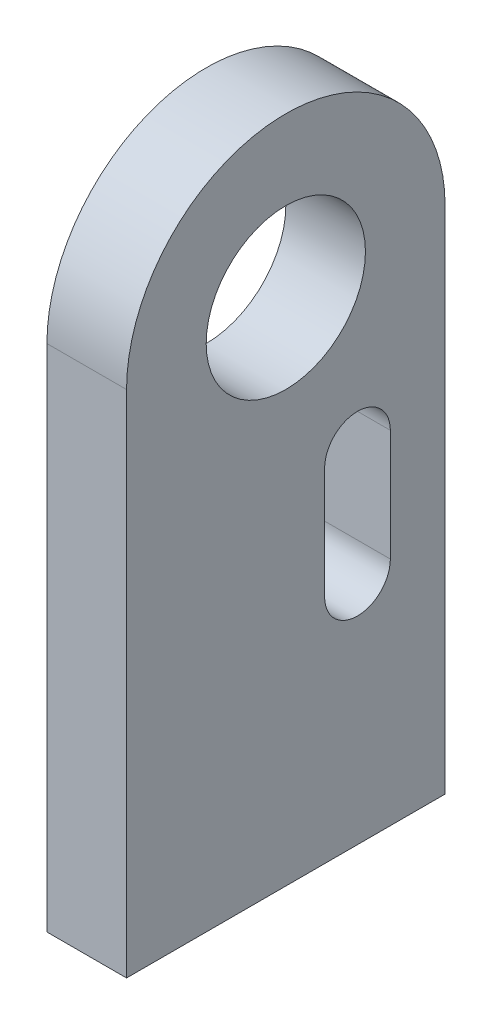
SolidWorks part; units mm, degrees
ref_plane "Front Plane" through (0, 0, 0) normal (0, 0, 1) x (1, 0, 0)
ref_plane "Top Plane" through (0, 0, 0) normal (0, 1, 0) x (1, 0, 0)
ref_plane "Right Plane" through (0, 0, 0) normal (1, 0, 0) x (0, 0, -1)
sketch "Sketch1" plane through (0, 0, 0) normal (1, 0, 0) x (0, 0, -1)
  line L0 (10, 0) -> (-10, 0)
  line L1 (-10, 32) -> (-10, 0)
  line L2 (0, 42) -> (0, 0) construction
  line L3 (10, 32) -> (10, 0)
  arc A0 (-10, 32) -> (10, 32) centre (0, 32) cw
  dimension "D1" = 10
extrude "Boss-Extrude1" add sketch "Sketch1" along normal blind 5 contours A0 L3 L0 L1
sketch "Sketch3" plane through (0, 0, 0) normal (-1, 0, 0) x (0, 0, 1)
  line L0 (-10, 32) -> (10, 32) construction
  line L1 (0, 32) -> (0, 0) construction
hole_wizard "Ø10.0mm Dowel Hole1" positions "3DSketch2" profile "Sketch4" hole size "Ø10.0" standard "ISO"
sketch3d "3DSketch2"
  point P0 (0, 32, 0)
sketch "Sketch4" plane through (0, 32, 0) normal (0, 1, 0) x (0, 0, 1)
  line L0 (0, 0) -> (0, 28.0043)
  line L1 (0, 28.0043) -> (5, 25)
  line L2 (5, 25) -> (5, 0)
  line L5 (5, 0) -> (0, 0)
  line L10 (0, 28.0043) -> (-5, 25) construction
  line L11 (0, -6.35) -> (0, 107.95) construction
  dimension "Hole Dia." = 10
  dimension "Hole Depth" = 25
  dimension "Drill Angle" = 118
sketch "Sketch5" plane through (5, 0, 0) normal (1, 0, 0) x (0, 0, -1)
  line L0 (0, 32) -> (10, 32) construction
  line L1 (10, 32) -> (-10, 32) construction
  line L2 (10, 0) -> (-10, 0) construction
  line L5 (4.5, 21.5) -> (4.5, 14.5) construction
  line L6 (6.5636, 21.5) -> (6.5636, 14.5)
  line L7 (2.4364, 21.5) -> (2.4364, 14.5)
  arc A0 (6.5636, 21.5) -> (2.4364, 21.5) centre (4.5, 21.5) ccw
  arc A1 (2.4364, 14.5) -> (6.5636, 14.5) centre (4.5, 14.5) ccw
  point P9 (4.5, 18)
  dimension "D1" = 18
extrude "Cut-Extrude1" cut sketch "Sketch5" against normal blind 10
sketch "Sketch6" plane through (0, 0, 0) normal (0, -1, 0) x (-1, 0, 0)
  line L0 (-2.5, -10) -> (-2.5, 10) construction
  line L1 (-5, -10) -> (0, -10) construction
  line L2 (-5, 10) -> (0, 10) construction
sketch "Sketch7" plane through (0, 0, 0) normal (0, -1, 0) x (-1, 0, 0)
  line L0 (0, 0) -> (-5, 0) construction
  line L1 (-5, 10) -> (-5, -10) construction
  line L2 (-2.5, 0) -> (-2.5, 5) construction
  line L3 (-2.5, 0) -> (-2.5, -5) construction
  dimension "D1" = 5
  dimension "D2" = 5
hole_wizard "M3 Tapped Hole1" positions "3DSketch3" profile "Sketch8" tap size "M3" standard "ISO"
sketch3d "3DSketch3"
  point P0 (2.5, 0, 5)
  point P3 (2.5, 0, -5)
sketch "Sketch8" plane through (2.5, 0, 5) normal (1, 0, 0) x (0, 0, -1)
  line L0 (0, 0) -> (0, 8.7511)
  line L1 (0, 8.7511) -> (1.25, 8)
  line L2 (1.25, 8) -> (1.25, 0)
  line L5 (1.25, 0) -> (0, 0)
  line L10 (0, 8.7511) -> (-1.25, 8) construction
  line L11 (0, -6.35) -> (0, 107.95) construction
  dimension "Tap Drill Dia." = 2.5
  dimension "Tap Drill Depth" = 8
  dimension "Drill Angle" = 118
cosmetic thread "Hole Thread1" parameters "D1"=6, "D2"=3
cosmetic thread "Hole Thread2" parameters "D1"=6, "D2"=3
